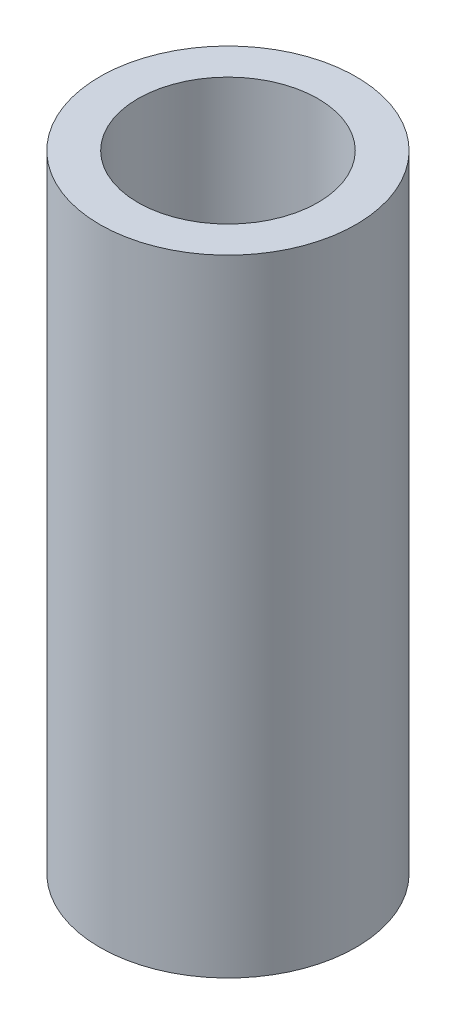
SolidWorks part; units mm, degrees
ref_plane "Front Plane" through (0, 0, 0) normal (0, 0, 1) x (1, 0, 0)
ref_plane "Top Plane" through (0, 0, 0) normal (0, 1, 0) x (1, 0, 0)
ref_plane "Right Plane" through (0, 0, 0) normal (1, 0, 0) x (0, 0, -1)
sketch "Sketch1" plane through (0, 0, 0) normal (0, 1, 0) x (1, 0, 0)
  circle A0 centre (0, 0) radius 32.5
  dimension "SLEEVE_OD" = 65
extrude "Boss-Extrude1" add sketch "Sketch1" along normal blind 158.8225
sketch "Sketch2" plane through (0, 0, 0) normal (0, 1, 0) x (1, 0, 0)
  circle A0 centre (0, 0) radius 22.8403
  dimension "BORE_D" = 45.6805
extrude "Cut-Extrude1" cut sketch "Sketch2" along normal through all
chamfer "Chamfer1" distance 3.7866 angle 59.773 rebuild error yes
